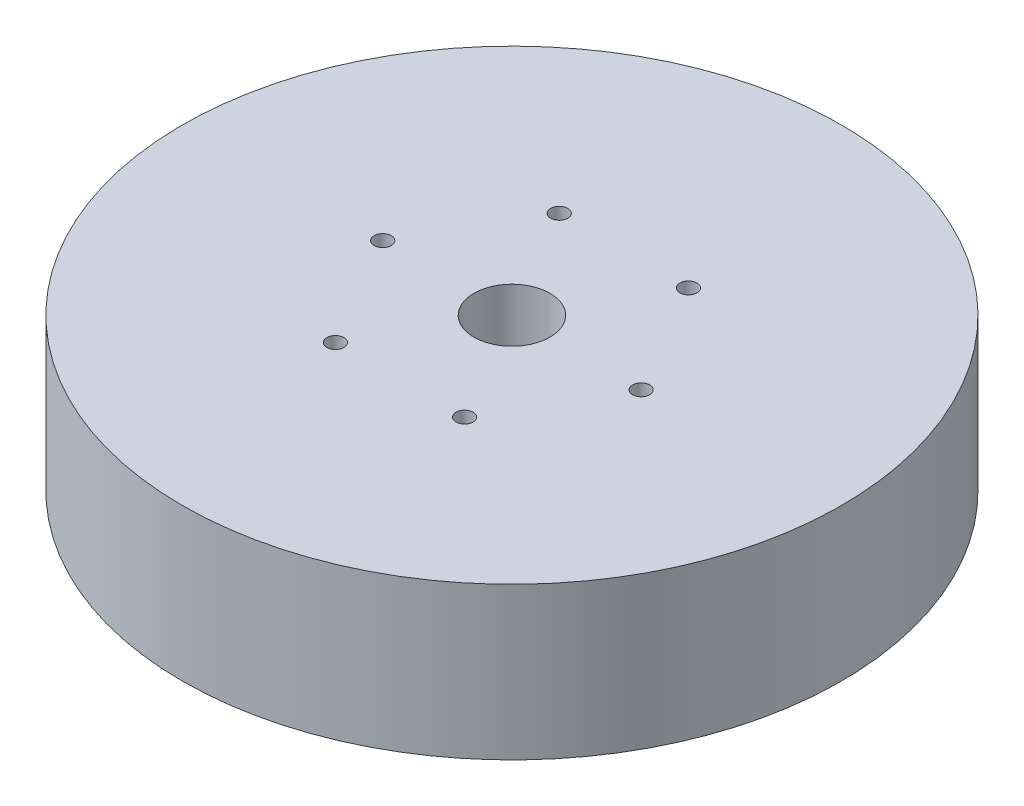
SolidWorks part; units mm, degrees
ref_plane "Front Plane" through (0, 0, 0) normal (0, 0, 1) x (1, 0, 0)
ref_plane "Top Plane" through (0, 0, 0) normal (0, 1, 0) x (1, 0, 0)
ref_plane "Right Plane" through (0, 0, 0) normal (1, 0, 0) x (0, 0, -1)
sketch "Sketch1" plane through (0, 0, 0) normal (0, 1, 0) x (1, 0, 0)
  circle A0 centre (0, 0) radius 65
  dimension "FLANGE_OD" = 130
extrude "Boss-Extrude1" add sketch "Sketch1" along normal blind 30
sketch "Sketch2" plane through (0, 0, 0) normal (0, 1, 0) x (1, 0, 0)
  circle A0 centre (0, 0) radius 7.5
  dimension "BORE_D" = 15
extrude "Cut-Extrude1" cut sketch "Sketch2" along normal through all
sketch "Sketch3" plane through (0, 30, 0) normal (0, 1, 0) x (1, 0, 0)
  circle A0 centre (0, 0) radius 25.4847 construction
  circle A1 centre (-25.4847, 0) radius 1.6901
  dimension "BOLT_D" = 3.3801
  dimension "BOLT_PCD" = 50.9694
extrude "Cut-Extrude2" cut sketch "Sketch3" against normal blind 20.3241
pattern_circular "CirPattern1" count 6 over 360 about axis through (0, 0, 0) along (0, 1, 0) of "Cut-Extrude2"
